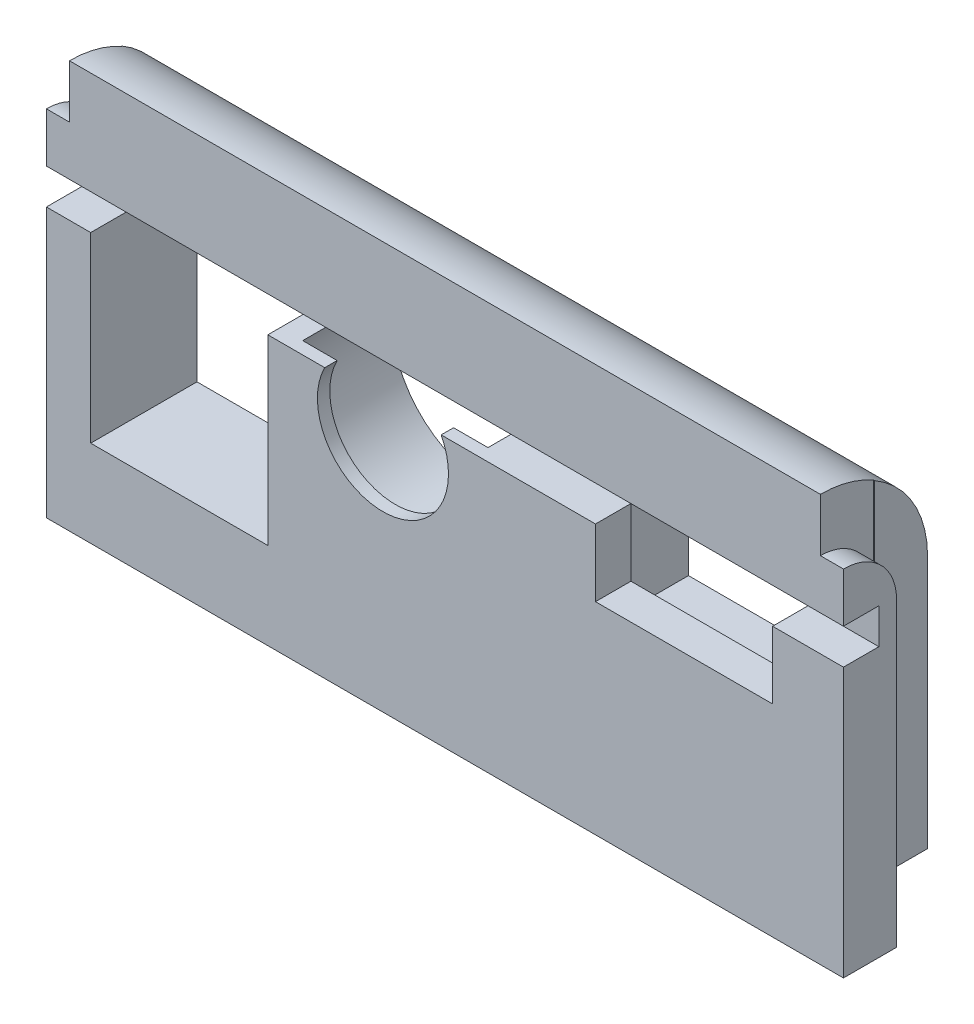
SolidWorks part; units mm, degrees
ref_plane "Plan de face" through (0, 0, 0) normal (0, 0, 1) x (1, 0, 0)
ref_plane "Plan de dessus" through (0, 0, 0) normal (0, 1, 0) x (1, 0, 0)
ref_plane "Plan de droite" through (0, 0, 0) normal (1, 0, 0) x (0, 0, -1)
sketch "Esquisse1" plane through (0, 0, 0) normal (0, 0, 1) x (1, 0, 0)
  line L1 (0, 0) -> (-45, 0)
  line L2 (0, 0) -> (0, 23)
  line L3 (0, 23) -> (-45, 23)
  line L4 (-45, 0) -> (-45, 23)
  dimension "D1" = 45
  dimension "D2" = 23
extrude "Boss.-Extru.1" add sketch "Esquisse1" along normal blind 6
sketch "Esquisse2" plane through (0, 0, 0) normal (0, 0, -1) x (-1, 0, 0)
  line L0 (0, 0) -> (0, 23) construction
  line L1 (0, 23) -> (1.25, 23)
  line L2 (0, 23) -> (0, 0)
  line L4 (1.25, 23) -> (1.25, 2.7)
  line L6 (45, 23) -> (45, 0) construction
  line L7 (1.25, 2.7) -> (43.75, 2.7)
  line L9 (0, 0) -> (45, 0)
  line L11 (45, 23) -> (43.75, 23)
  line L12 (45, 23) -> (45, 0)
  line L14 (43.75, 23) -> (43.75, 2.7)
  dimension "D1" = 42.5
  dimension "D2" = 2.7
  dimension "D3" = 23
extrude "Enlèv. mat.-Extru.1" cut sketch "Esquisse2" against normal blind 3
fillet "Congé1" radius 6 1 edges at (-22.5, 23, 0)
sketch "Esquisse6" plane through (0, 0, 0) normal (1, 0, 0) x (0, 0, -1)
  line L0 (0, 20.9684) -> (0, 9.3155) construction
  line L1 (0, 2.7) -> (0, 17) construction
  line L3 (-3, 22.2121) -> (-3, -1.1591) construction
  line L5 (-3, 17) -> (-3, 23.6165)
  line L6 (-3, 23.6165) -> (-6, 23.6165)
  line L7 (-6, 20) -> (-6, 23.6165)
  arc A0 (-3, 17) -> (-6, 20) centre (-6, 17) ccw
  dimension "D1" = 6
  dimension "D2" = 3
  dimension "D3" = 3
extrude "Enlèv. mat.-Extru.3" cut sketch "Esquisse6" against normal blind 1.3
ref_plane "Plan3" through (-22.5, 0, 0) normal (-1, 0, 0) x (0, 0, 1)
mirror "Symétrie2" about plane through (-22.5, 0, 0) normal (-1, 0, 0) of "Enlèv. mat.-Extru.3"
sketch "Esquisse7" plane through (0, 0, 6) normal (0, 0, 1) x (1, 0, 0)
  line L0 (-45, 20) -> (-45, 0) construction
  line L1 (-45, 17.2) -> (0, 17.2)
  line L2 (-45, 17.2) -> (-45, 15.2)
  line L3 (-45, 15.2) -> (0, 15.2)
  line L4 (0, 17.2) -> (0, 15.2)
  line L5 (0, 0) -> (0, 20) construction
  line L6 (-45, 0) -> (0, 0) construction
  dimension "D1" = 15.2
  dimension "D2" = 2
extrude "Enlèv. mat.-Extru.4" cut sketch "Esquisse7" against normal blind 2
sketch "Esquisse8" plane through (0, 0, 6) normal (0, 0, 1) x (1, 0, 0)
  line L1 (-42.5, 15.95) -> (-32.5, 15.95)
  line L2 (-42.5, 15.95) -> (-42.5, 4.9)
  line L3 (-42.5, 4.9) -> (-32.5, 4.9)
  line L4 (-32.5, 15.95) -> (-32.5, 4.9)
  line L5 (-45, 0) -> (0, 0) construction
  line L6 (-22.5, 23) -> (-22.5, 0) construction
  line L7 (-14, 15.7) -> (-4, 15.7)
  line L8 (-14, 15.7) -> (-14, 11.4)
  line L9 (-14, 11.4) -> (-4, 11.4)
  line L10 (-4, 15.7) -> (-4, 11.4)
  line L11 (-1.3, 23) -> (-43.7, 23) construction
  circle A0 centre (-26, 13.5) radius 5.5
  dimension "D5" = 4.3
  dimension "D9" = 13.5
  dimension "D11" = 11
  dimension "D2" = 4.9
  dimension "D3" = 10
  dimension "D4" = 11.05
  dimension "D6" = 10
  dimension "D7" = 11.4
  dimension "D8" = 10
  dimension "D10" = 3.5
  dimension "D12" = 8.5
extrude "Enlèv. mat.-Extru.5" cut sketch "Esquisse8" against normal through all
sketch "Esquisse9" plane through (0, 0, 0) normal (0, 0, -1) x (-1, 0, 0)
  line L0 (9, 15.7) -> (9, 11.4) construction
  line L1 (3.25, 17.8) -> (14.75, 17.8)
  line L2 (3.25, 17.8) -> (3.25, 9.3)
  line L3 (3.25, 9.3) -> (14.75, 9.3)
  line L4 (14.75, 17.8) -> (14.75, 9.3)
  line L5 (4, 15.7) -> (14, 15.7) construction
  line L6 (14, 11.4) -> (4, 11.4) construction
  line L7 (4, 13.55) -> (14, 13.55) construction
  line L8 (4, 11.4) -> (4, 15.7) construction
  line L9 (14, 15.7) -> (14, 11.4) construction
  dimension "D1" = 11.5
  dimension "D2" = 8.5
extrude "Enlèv. mat.-Extru.6" cut sketch "Esquisse9" against normal blind 4
sketch "Esquisse10" plane through (0, 0, 6) normal (0, 0, 1) x (1, 0, 0)
  line L0 (-30.0694, 17.2) -> (-21.9306, 17.2)
  line L1 (-31.2307, 15.2) -> (-20.7693, 15.2)
  arc A2 (-21.9306, 17.2) -> (-30.0694, 17.2) centre (-26, 13.5) ccw construction
  arc A3 (-31.2307, 15.2) -> (-20.7693, 15.2) centre (-26, 13.5) ccw construction
  arc A4 (-21.9306, 17.2) -> (-30.0694, 17.2) centre (-26, 13.5) ccw
  arc A5 (-31.2307, 15.2) -> (-20.7693, 15.2) centre (-26, 13.5) ccw
extrude "Boss.-Extru.2" add sketch "Esquisse10" against normal blind 0.7
sketch "Esquisse12" plane through (0, 0, 6) normal (0, 0, 1) x (1, 0, 0)
  line L0 (0, 17.2) -> (-45, 17.2) construction
  circle A0 centre (-26, 13.5) radius 3.7
extrude "Enlèv. mat.-Extru.8" cut sketch "Esquisse12" against normal blind 1
